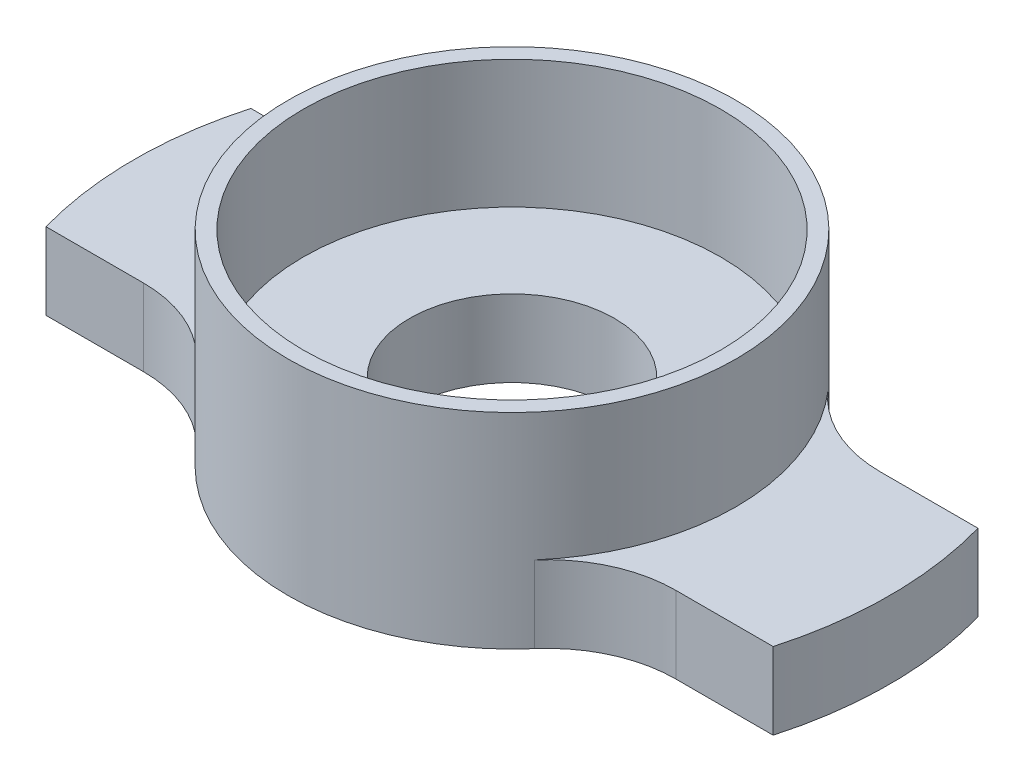
SolidWorks part; units mm, degrees
ref_plane "Front Plane" through (0, 0, 0) normal (0, 0, 1) x (1, 0, 0)
ref_plane "Top Plane" through (0, 0, 0) normal (0, 1, 0) x (1, 0, 0)
ref_plane "Right Plane" through (0, 0, 0) normal (1, 0, 0) x (0, 0, -1)
sketch "Sketch1" plane through (0, 0, 0) normal (0, 1, 0) x (1, 0, 0)
  circle A0 centre (0, 0) radius 16.3
  circle A1 centre (0, 0) radius 17.5
  dimension "D1" = 32.6
  dimension "D2" = 1.2
extrude "Boss-Extrude1" add sketch "Sketch1" along normal blind 10
sketch "Sketch2" plane through (0, 0, 0) normal (0, -1, 0) x (1, 0, 0)
  circle A0 centre (0, 0) radius 17.5
  circle A1 centre (0, 0) radius 17.5 construction
  circle A2 centre (0, 0) radius 8
  dimension "D1" = 16
extrude "Boss-Extrude2" add sketch "Sketch2" along normal blind 6
sketch "Sketch4" plane through (0, -6, 0) normal (0, -1, 0) x (1, 0, 0)
  line L0 (-28.3945, 8) -> (-8, 8)
  line L1 (-8, 8) -> (-8, -8)
  line L2 (-8, -8) -> (-28.3945, -8)
  line L3 (28.3945, -8) -> (8, -8)
  line L4 (8, -8) -> (8, 8)
  line L5 (8, 8) -> (28.3945, 8)
  arc A0 (-28.3945, 8) -> (-28.3945, -8) centre (0, 0) ccw
  arc A1 (28.3945, 8) -> (28.3945, -8) centre (0, 0) cw
  circle A2 centre (0, 0) radius 17.5 construction
  circle A3 centre (0, 0) radius 8 construction
  point P12 (-9.2591, 8.4069)
  point P13 (0, 0)
  point P14 (8.3838, -8.8215)
  point P15 (9.5815, 11.2629)
  point P18 (-8, 7.6238)
  dimension "D1" = 12
  dimension "D2" = 12
  dimension "D3" = 16
extrude "Boss-Extrude3" add sketch "Sketch4" against normal blind 6
fillet "Fillet1" radius 10 4 edges at (15.5644, -3, -8) (15.5644, -3, 8) (-15.5644, -3, -8) (-15.5644, -3, 8)
